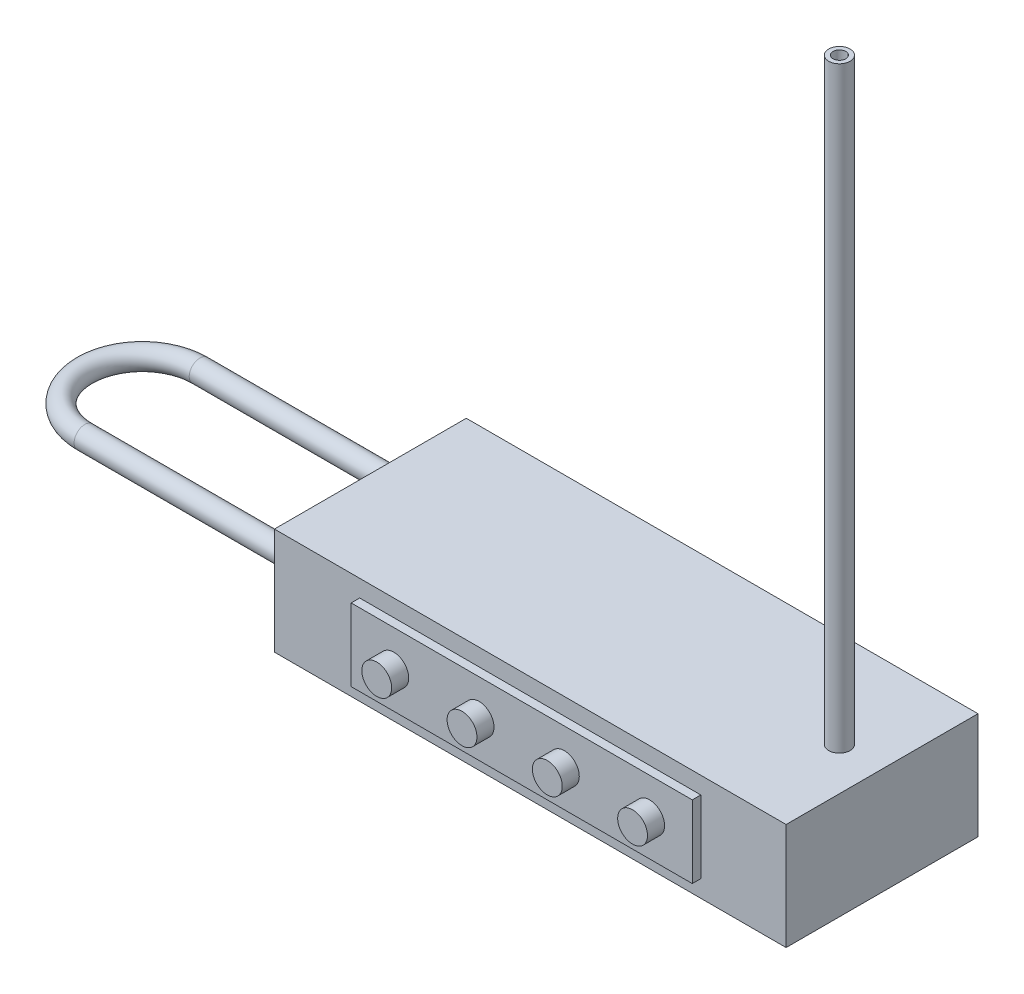
SolidWorks part; units mm, degrees
ref_plane "Front Plane" through (0, 0, 0) normal (0, 0, 1) x (1, 0, 0)
ref_plane "Top Plane" through (0, 0, 0) normal (0, 1, 0) x (1, 0, 0)
ref_plane "Right Plane" through (0, 0, 0) normal (1, 0, 0) x (0, 0, -1)
sketch "Sketch1" plane through (0, 0, 0) normal (0, 1, 0) x (1, 0, 0)
  line L1 (-60, 22.5) -> (60, 22.5)
  line L2 (-60, 22.5) -> (-60, -22.5)
  line L3 (-60, -22.5) -> (60, -22.5)
  line L4 (60, 22.5) -> (60, -22.5)
  line L5 (-60, 22.5) -> (60, -22.5) construction
  line L6 (-60, -22.5) -> (60, 22.5) construction
  point P0 (0, 0)
  dimension "D1" = 120
  dimension "D2" = 45
extrude "Boss-Extrude1" add sketch "Sketch1" along normal mid plane 25
sketch "Sketch3" plane through (0, 12.5, 0) normal (0, 1, 0) x (1, 0, 0)
  line L0 (0, 0) -> (60, 0) construction
  line L1 (60, -22.5) -> (60, 22.5) construction
  circle A0 centre (50, 0) radius 2.5
  circle A1 centre (50, 0) radius 1.5
  dimension "D2" = 5
  dimension "D3" = 10
  dimension "D1" = 1
extrude "Boss-Extrude2" add sketch "Sketch3" along normal blind 140
sketch "Sketch57" plane through (0, 0, 0) normal (0, 1, 0) x (1, 0, 0)
  line L0 (-60, 0) -> (-93.8677, 0) construction
  line L1 (-60, 22.5) -> (-60, -22.5) construction
  line L2 (-60, 13.5) -> (-113.4721, 13.5)
  line L3 (-60, -13.5) -> (-113.4721, -13.5)
  line L4 (60, 22.5) -> (-60, 22.5) construction
  arc A0 (-113.4721, 13.5) -> (-113.4721, -13.5) centre (-113.4721, 0) ccw
  dimension "D1" = 9
sweep "Sweep-Thin2" add path "Sketch57" circular profile diameter 5 parameters "D1"=1, "D3"=5
sketch "Sketch4" plane through (0, 0, 0) normal (0, 1, 0) x (1, 0, 0)
  line L0 (-60, 0) -> (-108.432, 0) construction
  line L1 (-60, 22.5) -> (-60, -22.5) construction
  line L2 (-60, 13.5) -> (-110.8307, 13.5)
  line L3 (-60, -13.5) -> (-75.261, -13.5)
  line L4 (60, 22.5) -> (-60, 22.5) construction
  arc A0 (-110.8307, 13.5) -> (-99.545, -21.3615) centre (-110.8307, -5.7575) ccw
  arc A1 (-99.545, -21.3615) -> (-75.261, -13.5) centre (-75.261, -54.9373) cw
  dimension "D1" = 9
sweep "Sweep-Thin1" [suppressed] add path "Sketch4" circular profile diameter 6 parameters "D1"=1, "D3"=6
sketch "Sketch53" plane through (0, 0, 22.5) normal (0, 0, 1) x (1, 0, 0)
  line L19 (-60, 12.5) -> (60, 12.5) construction
  line L20 (-40, 8.5) -> (40, 8.5)
  line L21 (-40, 8.5) -> (-40, -8.5)
  line L22 (-40, -8.5) -> (40, -8.5)
  line L23 (40, 8.5) -> (40, -8.5)
  line L24 (-40, 8.5) -> (40, -8.5) construction
  line L25 (-40, -8.5) -> (40, 8.5) construction
  line L26 (-60, 12.5) -> (-60, -12.5) construction
  point P25 (0, 0)
  dimension "D1" = 4
  dimension "D2" = 20
extrude "Boss-Extrude3" add sketch "Sketch53" along normal blind 2
sketch "Sketch54" plane through (0, 0, 24.5) normal (0, 0, 1) x (1, 0, 0)
  line L0 (-10, 0) -> (0, 0) construction
  circle A0 centre (-10, 0) radius 3.5
  dimension "D1" = 7
  dimension "D2" = 10
extrude "Boss-Extrude4" add sketch "Sketch54" along normal blind 4
pattern_linear "LPattern1" count 2 spacing 20 along (-1, 0, 0) count 3 spacing 20 along (1, 0, 0) of "Boss-Extrude4" pattern seed only yes
